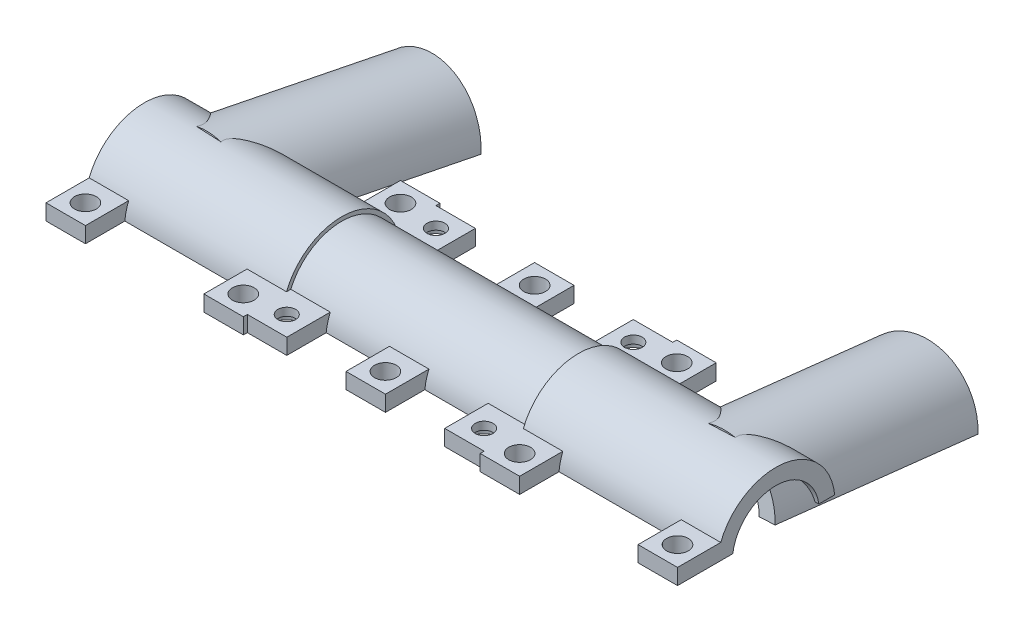
SolidWorks part; units mm, degrees
ref_plane "Front Plane" through (0, 0, 0) normal (0, 0, 1) x (1, 0, 0)
ref_plane "Top Plane" through (0, 0, 0) normal (0, 1, 0) x (1, 0, 0)
ref_plane "Right Plane" through (0, 0, 0) normal (1, 0, 0) x (0, 0, -1)
sketch "Sketch1" plane through (0, 0, 0) normal (1, 0, 0) x (0, 0, -1)
  line L0 (-49.4052, 0) -> (68.181, 0) construction
  line L1 (-13.9194, 1.5) -> (-9.8869, 1.5)
  line L2 (9.8869, 1.5) -> (13.9194, 1.5)
  arc A2 (9.8869, 1.5) -> (-9.8869, 1.5) centre (0, 0) ccw
  arc A3 (-13.9194, 1.5) -> (13.9194, 1.5) centre (0, 0) cw
  dimension "D1" = 1.5
  dimension "D2" = 10
  dimension "D3" = 14
extrude "Boss-Extrude2" add sketch "Sketch1" along normal mid plane 60
sketch "Sketch2" plane through (0, 1.5, 0) normal (0, -1, 0) x (1, 0, 0)
  line L0 (-30, -9.8869) -> (-30, -23.8869)
  line L1 (-30, -23.8869) -> (-20, -23.8869)
  line L2 (-20, -23.8869) -> (-20, -9.8869)
  line L3 (30, -9.8869) -> (-30, -9.8869) construction
  line L4 (-20, -9.8869) -> (-30, -9.8869)
  line L5 (-30, -13.9194) -> (-20, -23.8869) construction
  line L6 (-30, -23.8869) -> (-20, -13.9194) construction
  line L7 (30, -13.9194) -> (-30, -13.9194) construction
  line L8 (0, 27.2864) -> (0, -38.5559) construction
  line L9 (-39.4988, 0) -> (58.103, 0) construction
  line L10 (20, -23.8869) -> (20, -9.8869)
  line L11 (30, -23.8869) -> (20, -23.8869)
  line L12 (30, -9.8869) -> (30, -23.8869)
  line L13 (20, -9.8869) -> (30, -9.8869)
  line L14 (-20, 23.8869) -> (-20, 9.8869)
  line L15 (-30, 23.8869) -> (-20, 23.8869)
  line L16 (-30, 9.8869) -> (-30, 23.8869)
  line L17 (-20, 9.8869) -> (-30, 9.8869)
  line L18 (30, 23.8869) -> (20, 23.8869)
  line L19 (30, 9.8869) -> (30, 23.8869)
  line L20 (20, 9.8869) -> (30, 9.8869)
  line L21 (20, 23.8869) -> (20, 9.8869)
  line L22 (30, 9.8869) -> (-30, 9.8869) construction
  line L23 (-5, 9.8869) -> (5, 9.8869)
  line L24 (-5, 9.8869) -> (-5, 23.8869)
  line L25 (-5, 23.8869) -> (5, 23.8869)
  line L26 (5, 9.8869) -> (5, 23.8869)
  line L27 (-5, -23.8869) -> (5, -23.8869)
  line L28 (5, -9.8869) -> (5, -23.8869)
  line L29 (-5, -9.8869) -> (5, -9.8869)
  line L30 (-5, -9.8869) -> (-5, -23.8869)
  circle A0 centre (-25, -18.9031) radius 2.25
  circle A3 centre (25, 18.9031) radius 2.25
  circle A4 centre (25, -18.9031) radius 2.25
  circle A5 centre (-25, 18.9031) radius 2.25
  circle A6 centre (0, 18.9031) radius 2.75
  circle A7 centre (0, -18.9031) radius 2.75
  dimension "D3" = 5.5
  dimension "D4" = 4.5
  dimension "D1" = 10
  dimension "D2" = 14
extrude "Boss-Extrude3" add sketch "Sketch2" against normal blind 4
sketch "Sketch6" plane through (0, 1.5, 0) normal (0, -1, 0) x (1, 0, 0)
  circle A0 centre (-25, 18.9031) radius 4
  circle A1 centre (25, -18.9031) radius 4
  circle A2 centre (-25, -18.9031) radius 4
  circle A3 centre (25, 18.9031) radius 4
  dimension "D1" = 8
extrude "Cut-Extrude1" cut sketch "Sketch6" against normal blind 2
sketch "Sketch7" plane through (-30, 0, 0) normal (-1, 0, 0) x (0, 0, 1)
  line L0 (-25.7548, 0) -> (29.9478, 0) construction
  line L1 (-9.8869, 1.5) -> (-23.8869, 1.5) construction
  line L2 (23.8869, 1.5) -> (9.8869, 1.5) construction
  line L3 (-14.9248, 1.5) -> (-10.8972, 1.5)
  line L4 (10.8972, 1.5) -> (14.9248, 1.5)
  arc A0 (-10.8972, 1.5) -> (10.8972, 1.5) centre (0, 0) cw
  arc A1 (14.9248, 1.5) -> (-14.9248, 1.5) centre (0, 0) ccw
  dimension "D1" = 11
  dimension "D2" = 15
extrude "Boss-Extrude4" add sketch "Sketch7" along normal blind 50
sketch "Sketch8" plane through (0, 1.5, 0) normal (0, -1, 0) x (1, 0, 0)
  line L0 (-80, 24.8972) -> (-70, 14.9248) construction
  line L5 (-80, 10.8972) -> (-70, 10.8972)
  line L6 (-80, 10.8972) -> (-80, 24.8972)
  line L7 (-80, 24.8972) -> (-70, 24.8972)
  line L8 (-70, 10.8972) -> (-70, 24.8972)
  line L9 (-80, 14.9248) -> (-30, 14.9248) construction
  line L10 (-80, 14.9248) -> (-70, 24.8972) construction
  line L11 (-55, 14.9248) -> (-55, -27.4846) construction
  line L12 (-95.9106, 0) -> (39.2544, 0) construction
  line L13 (-30, 24.8972) -> (-40, 24.8972)
  line L14 (-40, 10.8972) -> (-40, 24.8972)
  line L15 (-30, 10.8972) -> (-40, 10.8972)
  line L16 (-30, 10.8972) -> (-30, 24.8972)
  line L21 (-30, -10.8972) -> (-30, -24.8972)
  line L22 (-30, -10.8972) -> (-40, -10.8972)
  line L23 (-40, -10.8972) -> (-40, -24.8972)
  line L24 (-30, -24.8972) -> (-40, -24.8972)
  circle A0 centre (-75, 19.911) radius 2.75
  circle A1 centre (-35, 19.911) radius 2.75
  circle A3 centre (-35, -19.911) radius 2.75
  dimension "D3" = 5.5
  dimension "D1" = 14
  dimension "D2" = 10
extrude "Boss-Extrude5" add sketch "Sketch8" against normal blind 4
mirror "Mirror1" about plane through (0, 0, 0) normal (1, 0, 0) of "Boss-Extrude4", "Boss-Extrude5"
sketch "Sketch_angle1" plane through (0, 1.5, 0) normal (0, -1, 0) x (1, 0, 0)
  line L0 (0, 0) -> (-80, 0) construction
  line L1 (-80, 10.8972) -> (-80, 24.8972) construction
  line L2 (-65, 0) -> (-54.9989, -190.8326) construction
  line L3 (-65, 0) -> (-65, -122.5894) construction
  dimension "D1" = 3
  dimension "D2" = 15
ref_plane "Plane3" through (-64.822, 0, -3.3972) normal (0.9986, 0, 0.0523) x (0.0523, 0, -0.9986)
sketch "Sketch_angle2" plane through (-64.822, 0, -3.3972) normal (0.9986, 0, 0.0523) x (0.0523, 0, -0.9986)
  line L0 (0, 0) -> (100, 0) construction
  line L1 (0, 0) -> (50, -7.9192) construction
  dimension "D1" = 9
  dimension "D2" = 100
  dimension "D3" = 50
ref_plane "Plane4" through (-62.2052, -7.9192, -53.3287) normal (0.0517, -0.1564, -0.9863) x (-0.9986, 0.0004, -0.0524)
sketch "Sketch13" plane through (-62.2052, -7.9192, -53.3287) normal (0.0517, -0.1564, -0.9863) x (-0.9986, 0.0004, -0.0524)
  line L0 (13.579, 0) -> (-20.9928, 0) construction
  line L1 (10.8972, 1.5) -> (14.7238, 1.5)
  line L2 (-14.7238, 1.5) -> (-10.8972, 1.5)
  arc A0 (10.8972, 1.5) -> (-10.8972, 1.5) centre (0, 0) ccw
  arc A1 (14.7238, 1.5) -> (-14.7238, 1.5) centre (0, 0) ccw
  dimension "D1" = 11
  dimension "D3" = 14.8
  dimension "D2" = 1.5
extrude "Boss-Extrude6" add sketch "Sketch13" against normal blind 55
mirror "Mirror2" about plane through (0, 0, 0) normal (1, 0, 0) of "Boss-Extrude6"
